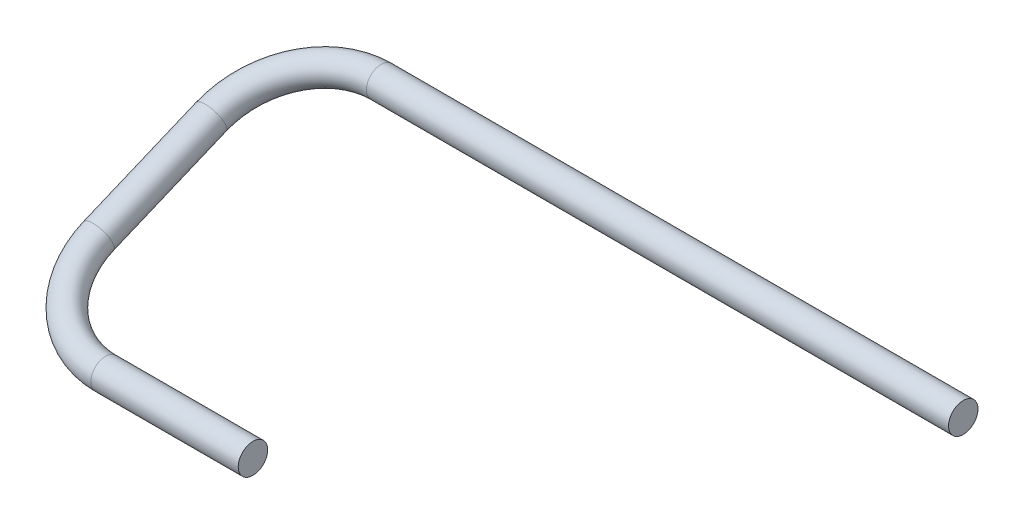
SolidWorks part; units mm, degrees
ref_plane "Front Plane" through (0, 0, 0) normal (0, 0, 1) x (1, 0, 0)
ref_plane "Top Plane" through (0, 0, 0) normal (0, 1, 0) x (1, 0, 0)
ref_plane "Right Plane" through (0, 0, 0) normal (1, 0, 0) x (0, 0, -1)
sketch3d "3DSketch1"
  line L0 (-296.6327, 1724.025, -224.028) -> (-547.4105, 1724.025, -224.028)
  line L1 (-282.5357, 1724.025, -224.028) -> (-296.6327, 1724.025, -224.028) construction
  line L2 (-483.9105, 1674.495, -105.2986) -> (-547.4105, 1674.495, -105.2986)
  line L3 (-464.1139, 1674.495, -105.2986) -> (-427.507, 1674.495, -105.2986) construction
  line L4 (-585.5105, 1709.3562, -188.865) -> (-585.5105, 1689.1638, -140.4616)
  arc A0 (-547.4105, 1674.495, -105.2986) -> (-585.5105, 1689.1638, -140.4616) centre (-547.4105, 1689.1638, -140.4616) ccw
  arc A1 (-547.4105, 1724.025, -224.028) -> (-585.5105, 1709.3562, -188.865) centre (-547.4105, 1709.3562, -188.865) ccw
  point P10 (-585.5105, 1674.495, -105.2986)
  point P11 (-547.4105, 1654.0009, -155.1304)
  point P14 (-585.5105, 1724.025, -224.028)
  point P15 (-547.4105, 1744.5191, -174.1962)
  dimension "D2" = 38.1
  dimension "D1" = 101.6
sweep "Sweep1" add path "3DSketch1" circular profile diameter 12.7 parameters "D3"=12.7
ref_plane "Plane1" through (0, 1388.8658, 579.3891) normal (0, 0.9229, 0.385) x (1, 0, 0)
